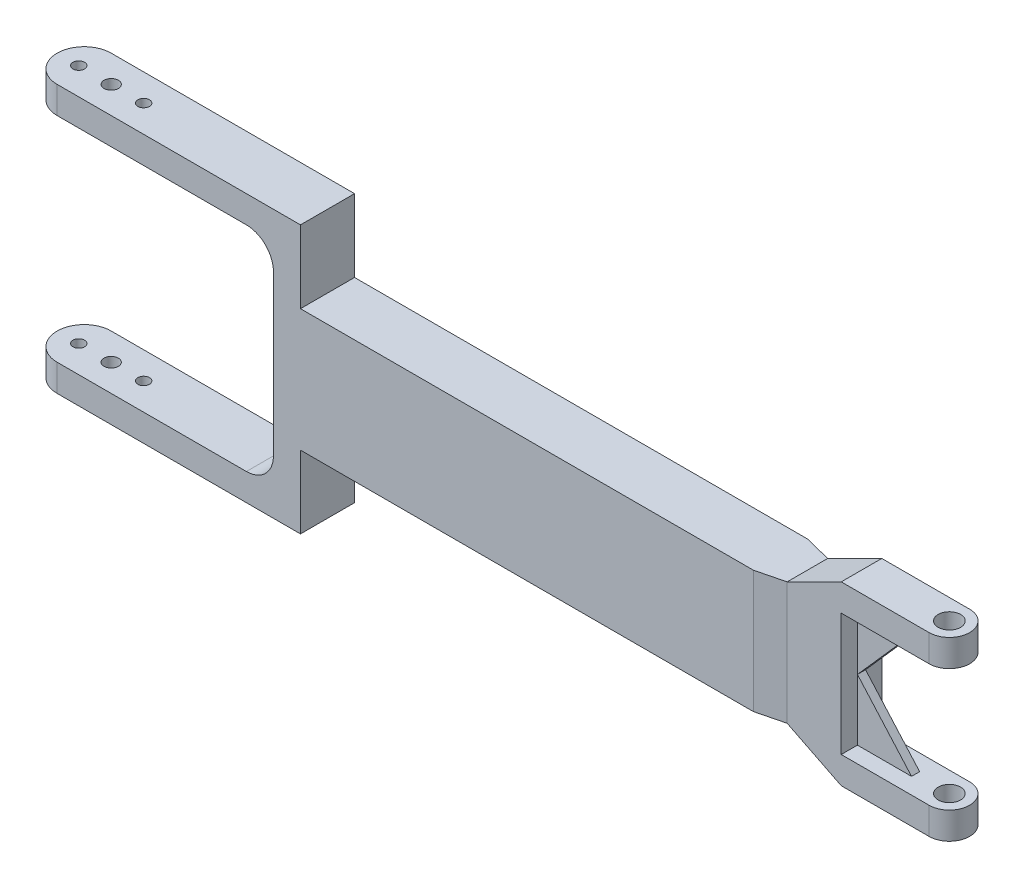
SolidWorks part; units mm, degrees
material "ABS"
ref_plane "前视基准面" through (0, 0, 0) normal (0, 0, 1) x (1, 0, 0)
ref_plane "上视基准面" through (0, 0, 0) normal (0, 1, 0) x (1, 0, 0)
ref_plane "右视基准面" through (0, 0, 0) normal (1, 0, 0) x (0, 0, -1)
other "Configuration Table"
sketch "草图2" plane through (0, 0, 0) normal (0, 0, 1) x (1, 0, 0)
  line L0 (0, 12.65) -> (0, -12.65)
  line L1 (0, 12.65) -> (40, 12.65)
  line L2 (40, 12.65) -> (40, 22.65)
  line L3 (40, 22.65) -> (-10, 22.65)
  line L4 (-10, 22.65) -> (-10, -22.65)
  line L5 (-10, -22.65) -> (40, -22.65)
  line L6 (40, -22.65) -> (40, -12.65)
  line L7 (40, -12.65) -> (0, -12.65)
  line L8 (-207.5, -39.5) -> (-207.5, 39.5)
  line L9 (-207.5, -39.5) -> (-297.5, -39.5)
  line L10 (-297.5, -39.5) -> (-297.5, -49.5)
  line L11 (-297.5, -49.5) -> (-197.5, -49.5)
  line L12 (-197.5, -49.5) -> (-197.5, 49.5)
  line L13 (-197.5, 49.5) -> (-297.5, 49.5)
  line L14 (-297.5, 49.5) -> (-297.5, 39.5)
  line L15 (-297.5, 39.5) -> (-207.5, 39.5)
  line L16 (-10, 22.65) -> (-197.5, 22.65)
  line L17 (-10, -22.65) -> (-197.5, -22.65)
  point P4 (0, 0)
  point P12 (-207.5, 0)
  dimension "D1" = 25.3
  dimension "D2" = 40
  dimension "D3" = 10
  dimension "D4" = 10
  dimension "D5" = 79
  dimension "D6" = 90
  dimension "D7" = 10
  dimension "D8" = 10
  dimension "D9" = 10
  dimension "D10" = 187.5
extrude "凸台-拉伸1" add sketch "草图2" along normal mid plane 20 contours L17 L4 L16 L12 | L14 L15 L8 L9 L10 L11 L12 L13 region at (-103.75, 0, 0) region at (-198.9072, 0, 0)
extrude "凸台-拉伸2" add sketch "草图2<3>" along normal mid plane 15 contours L6 L7 L0 L1 L2 L3 L4 L5 region at (-0.6747, 0, 0)
sketch "草图2<3>" plane through (0, 0, 0) normal (0, 0, 1) x (1, 0, 0) same geometry as "草图2"
chamfer "倒角1" distance 20 distance2 5 1 edges at (-10, 0, 10) first distance on face at (-201.25, 0, 10)
chamfer "倒角2" distance 5 distance2 20 1 edges at (-10, 0, -10) first distance on face at (-10, 0, -8.75)
sketch "草图7" plane through (0, 0, 7.5) normal (0, 0, 1) x (1, 0, 0)
  line L0 (40, 22.65) -> (-20, 22.65) construction
  line L1 (40, 32.65) -> (0, 32.65)
  line L2 (40, 32.65) -> (40, 22.65)
  line L3 (40, 22.65) -> (0, 22.65)
  line L4 (0, 32.65) -> (0, 22.65)
  line L5 (20, 22.65) -> (20, 32.65) construction
  line L6 (40, 27.65) -> (0, 27.65) construction
  line L7 (0, 12.65) -> (0, -12.65) construction
  line L8 (40, 12.65) -> (40, 22.65) construction
  line L9 (0, 32.65) -> (-20, 22.65)
  line L10 (11, 0) -> (-11, 0) construction
  line L11 (40, -32.65) -> (40, -22.65)
  line L12 (0, -32.65) -> (-20, -22.65)
  line L13 (40, -32.65) -> (0, -32.65)
  line L14 (0, 22.65) -> (0, 12.65)
  line L15 (0, -12.65) -> (0, -22.65)
  line L22 (40, -22.65) -> (40, -12.65)
  line L23 (40, -12.65) -> (0, -12.65)
  line L24 (0, -12.65) -> (0, 12.65)
  line L25 (0, 12.65) -> (40, 12.65)
  line L26 (40, 12.65) -> (40, 22.65)
  line L27 (40, 22.65) -> (-20, 22.65)
  line L28 (-20, 22.65) -> (-20, -22.65)
  line L29 (-20, -22.65) -> (40, -22.65)
  line L30 (40, -22.65) -> (40, -12.65)
  line L31 (40, -12.65) -> (0, -12.65)
  line L32 (0, -12.65) -> (0, 12.65)
  line L33 (0, 12.65) -> (40, 12.65)
  line L34 (40, 12.65) -> (40, 22.65)
  line L35 (40, 22.65) -> (-20, 22.65)
  line L36 (-20, 22.65) -> (-20, -22.65)
  line L37 (-20, -22.65) -> (40, -22.65)
  point P120 (20, 27.65)
  line M14 (40, -22.65) -> (40, -12.65)
  line M15 (40, -12.65) -> (0, -12.65)
  line M17 (0, 12.65) -> (40, 12.65)
  line M18 (40, 12.65) -> (40, 22.65)
  line M19 (40, 22.65) -> (-20, 22.65)
  line M21 (-20, -22.65) -> (40, -22.65)
  dimension "D1" = 10
  dimension "D2" = 0
extrude "凸台-拉伸6" add sketch "草图7" against normal up to surface (15 mm away) contours L4 L9 M19 | L1 L4 L2 M19 | L13 L11 L12 M21 region at (20, 27.65, 7.5) region at (-6.6667, 25.9833, 7.5) region at (14.6667, -27.3167, 7.5) up to face at (15, 0, -7.5)
extrude "切除-拉伸3" cut sketch "草图7<3>" against normal up to surface (15 mm away) contours L14 M19 M17 M18 | L15 M15 M21 M14 region at (20, 17.65, 7.5) region at (20, -17.65, 7.5) up to face at (12, 0, -7.5)
sketch "草图7<3>" plane through (0, 0, 7.5) normal (0, 0, 1) x (1, 0, 0) same geometry as "草图7"
sketch "草图8" plane through (0, 0, 0) normal (0, 0, 1) x (1, 0, 0)
  line L0 (0, 0) -> (20, 22.65)
  line L1 (0, 0) -> (20, -22.65)
  line L10 (0, 22.65) -> (40, 22.65)
  line L11 (40, 22.65) -> (40, 32.65)
  line L12 (40, 32.65) -> (0, 32.65)
  line L13 (0, 32.65) -> (-20, 22.65)
  line L14 (-20, 22.65) -> (-20, -22.65)
  line L15 (-20, -22.65) -> (0, -32.65)
  line L16 (0, -32.65) -> (40, -32.65)
  line L17 (40, -32.65) -> (40, -22.65)
  line L18 (40, -22.65) -> (0, -22.65)
  line L19 (0, -22.65) -> (0, 22.65)
  line L20 (0, 22.65) -> (40, 22.65)
  line L21 (40, 22.65) -> (40, 32.65)
  line L22 (40, 32.65) -> (0, 32.65)
  line L23 (0, 32.65) -> (-20, 22.65)
  line L24 (-20, 22.65) -> (-20, -22.65)
  line L25 (-20, -22.65) -> (0, -32.65)
  line L26 (0, -32.65) -> (40, -32.65)
  line L27 (40, -32.65) -> (40, -22.65)
  line L28 (40, -22.65) -> (0, -22.65)
  line L29 (0, -22.65) -> (0, 22.65)
  point P8 (0, 0)
  dimension "D1" = 0
extrude "凸台-拉伸7" add sketch "草图8" along normal mid plane 3 contours L29 L0 L20 | L29 L28 L1 region at (6.6667, 15.1, 0) region at (6.6667, -15.1, 0)
sketch "草图3" plane through (0, 49.5, 0) normal (0, 1, 0) x (1, 0, 0)
  line L0 (-297.5, 0) -> (-197.5, 0) construction
  line L4 (-197.5, 10) -> (-297.5, 10)
  line L5 (-297.5, 10) -> (-297.5, -10)
  line L6 (-297.5, -10) -> (-197.5, -10)
  line L7 (-197.5, -10) -> (-197.5, 10)
  line L8 (-197.5, 10) -> (-297.5, 10)
  line L9 (-297.5, 10) -> (-297.5, -10)
  line L10 (-297.5, -10) -> (-197.5, -10)
  line L11 (-197.5, -10) -> (-197.5, 10)
  circle A0 centre (-277.5, 0) radius 2.65
  circle A1 centre (-289.5, 0) radius 2.15
  circle A2 centre (-265.5, 0) radius 2.15
  arc A3 (-287.5, 10) -> (-287.5, -10) centre (-287.5, 0) ccw
  line M6 (-297.5, 10) -> (-297.5, -10)
  line M7 (-297.5, -10) -> (-197.5, -10)
  dimension "D2" = 5.3
  dimension "D5" = 4.3
  dimension "D7" = 180
  dimension "D3" = 12
  dimension "D4" = 12
  dimension "D6" = 80
  dimension "D1" = 0
extrude "切除-拉伸1" cut sketch "草图3" against normal through all contours A3 L8 M6 | A3 L9 M7 | L0 A1 | A1 L0 | A0 L0 | L0 A0 | A2 L0 | L0 A2 region at (-265.5, 49.5, 0.9125) region at (-265.5, 49.5, -0.9125) region at (-277.5, 49.5, 1.1247) region at (-277.5, 49.5, -1.1247) region at (-295.2663, 49.5, 7.7663) region at (-295.2663, 49.5, -7.7663) region at (-289.5, 49.5, 0.9125) region at (-289.5, 49.5, -0.9125)
sketch "草图4" plane through (0, 22.65, 0) normal (0, 1, 0) x (1, 0, 0)
  line L0 (0, 0) -> (40, 0) construction
  line L1 (40, -7.5) -> (40, 7.5) construction
  line L2 (40, 7.5) -> (40, -7.5) construction
  line L3 (0, 7.5) -> (40, 7.5) construction
  line L15 (40, 7.5) -> (0, 7.5)
  line L24 (0, 7.5) -> (0, -7.5)
  line L25 (0, -7.5) -> (40, -7.5)
  line L26 (40, -7.5) -> (40, 7.5)
  line L27 (40, 7.5) -> (0, 7.5)
  line L28 (0, 7.5) -> (0, -7.5)
  line L29 (0, -7.5) -> (40, -7.5)
  line L30 (40, -7.5) -> (40, 7.5)
  circle A0 centre (32.5, 0) radius 7.5
  circle A1 centre (32.5, 0) radius 4.15
  point P13 (31.4285, 0)
  dimension "D2" = 8.3
  dimension "D1" = 0
extrude "切除-拉伸2" cut sketch "草图4" against normal through all both and the other way through all contours A1 L0 | L0 A1 | A0 | A0 region at (32.5, 22.65, 1.7613) region at (32.5, 22.65, -1.7613) region at (38.3247, 22.65, -5.8247) region at (38.3247, 22.65, 5.8247)
fillet "圆角1" radius 10 2 edges at (-207.5, 39.5, 0) (-207.5, -39.5, 0)
